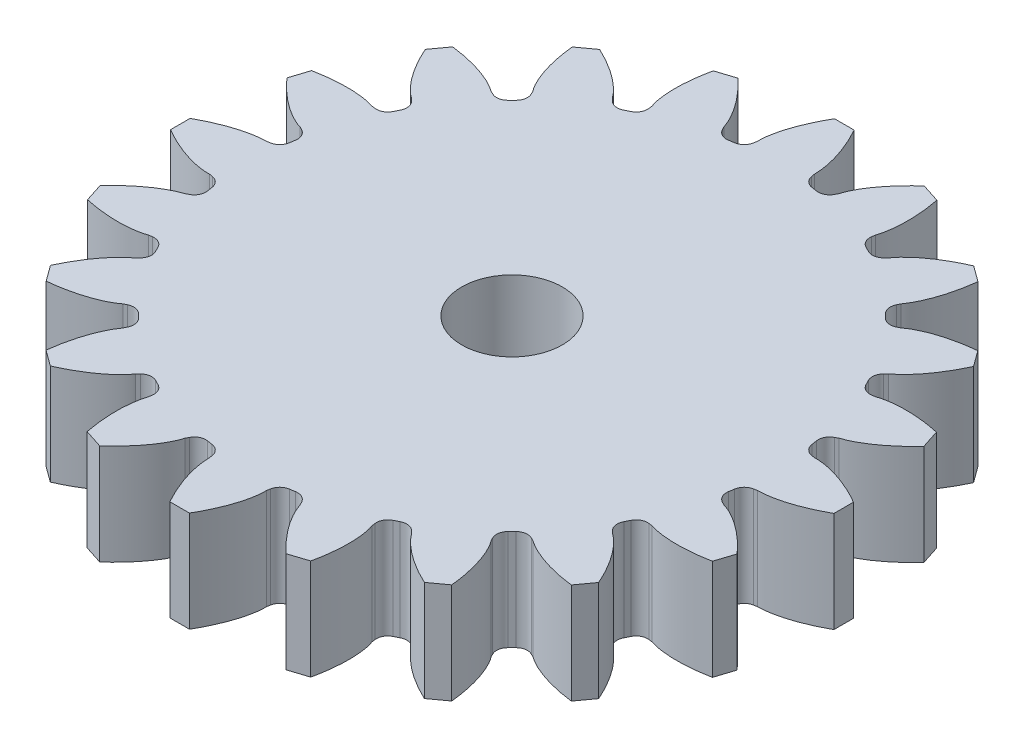
SolidWorks part; units mm, degrees
ref_plane "Front" through (0, 0, 0) normal (0, 0, 1) x (1, 0, 0)
ref_plane "Top" through (0, 0, 0) normal (0, 1, 0) x (1, 0, 0)
ref_plane "Right" through (0, 0, 0) normal (1, 0, 0) x (0, 0, -1)
sketch "Sketch1" plane through (0, 0, 0) normal (0, 1, 0) x (1, 0, 0)
  line L0 (0, 0) -> (0, 33.4864) construction
  line L1 (-0.9054, 16.5) -> (0.9054, 16.5) construction
  line L3 (-0.9054, 16.5) -> (-1.516, 13.0371) construction
  line L6 (0.9054, 16.5) -> (1.516, 13.0371) construction
  line L9 (-1.1781, 14.9537) -> (1.1781, 14.9537) construction
  line L11 (-1.4129, 13.6219) -> (1.4129, 13.6219) construction
  line L13 (-0.4686, 16.5) -> (0.504, 16.5)
  line L16 (-1.4129, 13.6219) -> (-1.516, 13.0371)
  line L18 (1.4129, 13.6219) -> (1.516, 13.0371)
  circle A1 centre (0, 0) radius 15 construction
  circle A13 centre (0, 0) radius 13.125
  circle A14 centre (0, 0) radius 16.5 construction
  circle A15 centre (0, 0) radius 13.695 construction
  spline S0 degree 4 poles (1.4102, 13.5342) (1.4114, 13.5591) (1.4129, 13.6023) (1.4133, 13.6384) (1.4119, 13.7271) (1.4082, 13.797) (1.402, 13.8861) (1.3927, 13.976) (1.381, 14.0711) (1.3671, 14.1636) (1.3514, 14.2572) (1.3338, 14.3496) (1.3144, 14.4426) (1.2882, 14.5579) (1.2535, 14.696) (1.2094, 14.8549) (1.1529, 15.036) (1.0927, 15.2133) (1.026, 15.3926) (0.9582, 15.5643) (0.881, 15.7439) (0.8085, 15.9062) (0.7182, 16.0924) (0.6478, 16.2344) (0.5404, 16.4348) (0.4895, 16.5269) (0.418, 16.6521) (0.3809, 16.7153) (0.3618, 16.7475) (0.3521, 16.7638) knots 0 0 0 0 0 0.024861 0.043163 0.061467 0.087193 0.114648 0.142103 0.169558 0.197014 0.224469 0.251924 0.279379 0.307336 0.362246 0.417157 0.472067 0.526978 0.581888 0.636798 0.691709 0.746619 0.80153 0.85644 0.911351 0.955675 0.977838 1 1 1 1 1 construction
  spline S1 degree 4 poles (1.4129, 13.6219) (1.413, 13.6359) (1.4129, 13.6637) (1.4119, 13.7271) (1.4082, 13.797) (1.402, 13.8861) (1.3927, 13.976) (1.381, 14.0711) (1.3671, 14.1636) (1.3514, 14.2572) (1.3338, 14.3496) (1.3144, 14.4426) (1.2882, 14.5579) (1.2535, 14.696) (1.2094, 14.8549) (1.1529, 15.036) (1.0927, 15.2133) (1.026, 15.3926) (0.9582, 15.5643) (0.881, 15.7439) (0.8085, 15.9062) (0.7182, 16.0924) (0.6478, 16.2344) (0.5632, 16.3923) (0.5244, 16.4634) (0.504, 16.5) knots 0.024861 0.024861 0.024861 0.024861 0.024861 0.043163 0.061467 0.087193 0.114648 0.142103 0.169558 0.197014 0.224469 0.251924 0.279379 0.307336 0.362246 0.417157 0.472067 0.526978 0.581888 0.636798 0.691709 0.746619 0.80153 0.85644 0.911345 0.911345 0.911345 0.911345 0.911345
  spline S2 degree 4 poles (-1.4129, 13.6219) (-1.4134, 13.6264) (-1.4144, 13.6391) (-1.4156, 13.6631) (-1.4165, 13.7024) (-1.416, 13.7525) (-1.4137, 13.8174) (-1.4086, 13.8938) (-1.4006, 13.9779) (-1.3893, 14.0694) (-1.3758, 14.1606) (-1.3601, 14.2515) (-1.3425, 14.342) (-1.319, 14.4515) (-1.2876, 14.5826) (-1.2463, 14.7355) (-1.194, 14.9083) (-1.135, 15.0839) (-1.0721, 15.2561) (-1.0032, 15.4293) (-0.9327, 15.5963) (-0.854, 15.7689) (-0.7785, 15.9277) (-0.6879, 16.1045) (-0.613, 16.2469) (-0.5078, 16.4333) (-0.4437, 16.5431) (-0.3666, 16.671) (-0.3311, 16.7275) (-0.3094, 16.7623) knots 0 0 0 0 0 0.005377 0.015084 0.028532 0.04661 0.064855 0.092111 0.119476 0.146842 0.174209 0.201575 0.228941 0.256307 0.307035 0.361767 0.4165 0.471232 0.525964 0.580697 0.635429 0.690161 0.744894 0.799626 0.854358 0.909091 0.954545 1 1 1 1 1 construction
  spline S3 degree 4 poles (-1.4129, 13.6219) (-1.4134, 13.6264) (-1.4144, 13.6391) (-1.4156, 13.6631) (-1.4165, 13.7024) (-1.416, 13.7525) (-1.4137, 13.8174) (-1.4086, 13.8938) (-1.4006, 13.9779) (-1.3893, 14.0694) (-1.3758, 14.1606) (-1.3601, 14.2515) (-1.3425, 14.342) (-1.319, 14.4515) (-1.2876, 14.5826) (-1.2463, 14.7355) (-1.194, 14.9083) (-1.135, 15.0839) (-1.0721, 15.2561) (-1.0032, 15.4293) (-0.9327, 15.5963) (-0.854, 15.7689) (-0.7785, 15.9277) (-0.6879, 16.1045) (-0.613, 16.2469) (-0.5306, 16.3929) (-0.4897, 16.4638) (-0.4686, 16.5) knots 0 0 0 0 0 0.005377 0.015084 0.028532 0.04661 0.064855 0.092111 0.119476 0.146842 0.174209 0.201575 0.228941 0.256307 0.307035 0.361767 0.4165 0.471232 0.525964 0.580697 0.635429 0.690161 0.744894 0.799626 0.854358 0.909087 0.909087 0.909087 0.909087 0.909087
  point P9 (0, 0)
  point P20 (0, 16.5)
  dimension "D2" = 26.25
  dimension "D3" = 33
  dimension "D1" = 30
  dimension "D6" = 27.39
  dimension "D4" = 20
  dimension "D5" = 2.3562
extrude "Boss-Extrude1" add sketch "Sketch1" along normal blind 5 contours A13 region at (0, 0, 0)
extrude "Boss-Extrude2" add sketch "Sketch1<4>" along normal blind 5 contours S3 A13 S1 L13 region at (0.0011, 0, -14.5544)
sketch "Sketch1<4>" plane through (0, 0, 0) normal (0, 1, 0) x (1, 0, 0) same geometry as "Sketch1"
fillet "Fillet2" radius 0.57 2 edges at (-1.516, 2.5, -13.0371) (1.516, 2.5, -13.0371)
pattern_circular "CirPattern5" count 20 over 360 about axis through (0, 5, 0) along (0, 1, 0) of "Boss-Extrude2", "Fillet2"
sketch "Sketch2" plane through (0, 5, 0) normal (0, 1, 0) x (1, 0, 0)
  circle A0 centre (0, 0) radius 2.5
  dimension "D1" = 5
extrude "Cut-Extrude1" cut sketch "Sketch2" against normal up to next
equation "\"Reference_Diameter\" = 30"
equation "\"Reference_Radius\"= \"Reference_Diameter\" / 2"
equation "\"Module\"= \"Reference_Diameter\" / \"Teeth\""
equation "\"Teeth\" = 20'The Number of Teeth"
equation "\"Pitch\"= \"Module\" * PI"
equation "\"Tooth_Depth\"= \"Module\" * 2.25"
equation "\"Addendum\"= \"Module\"'Distance above reference"
equation "\"Dedendum\"= \"Module\" * 1.25'Distance below reference"
equation "\"Tooth_Thickness\"= ( \"Module\" * PI ) / 2"
equation "\"Tip_Diameter\"= \"Reference_Diameter\" + ( 2 * \"Module\" )"
equation "\"Root_Diameter\"= \"Reference_Diameter\" - ( 2.5 * \"Module\" )"
equation "\"Pressure_Angle\"= 20deg"
equation "\"D2@Sketch1\"= \"Root_Diameter\""
equation "\"D1@Sketch1\"=\"Reference_Diameter\""
equation "\"D4@Sketch1\"=\"Pressure_Angle\""
equation "\"D5@Sketch1\"=\"Tooth_Thickness\""
equation "\"Pressure_Angle_Rads\"= ( \"Pressure_Angle\" * 2 * PI ) / 180deg"
equation "\"Dedendum_Fillet_Radius\"= 0.38 * \"Module\""
equation "\"D6@Sketch1\"=\"Root_Diameter\"+(2*0.38*\"Module\")"
equation "\"D3@Sketch1\"=\"Tip_Diameter\""
equation "\"D1@CirPattern5\"=\"Teeth\""
equation "\"D1@Fillet2\"=\"Dedendum_Fillet_Radius\""
